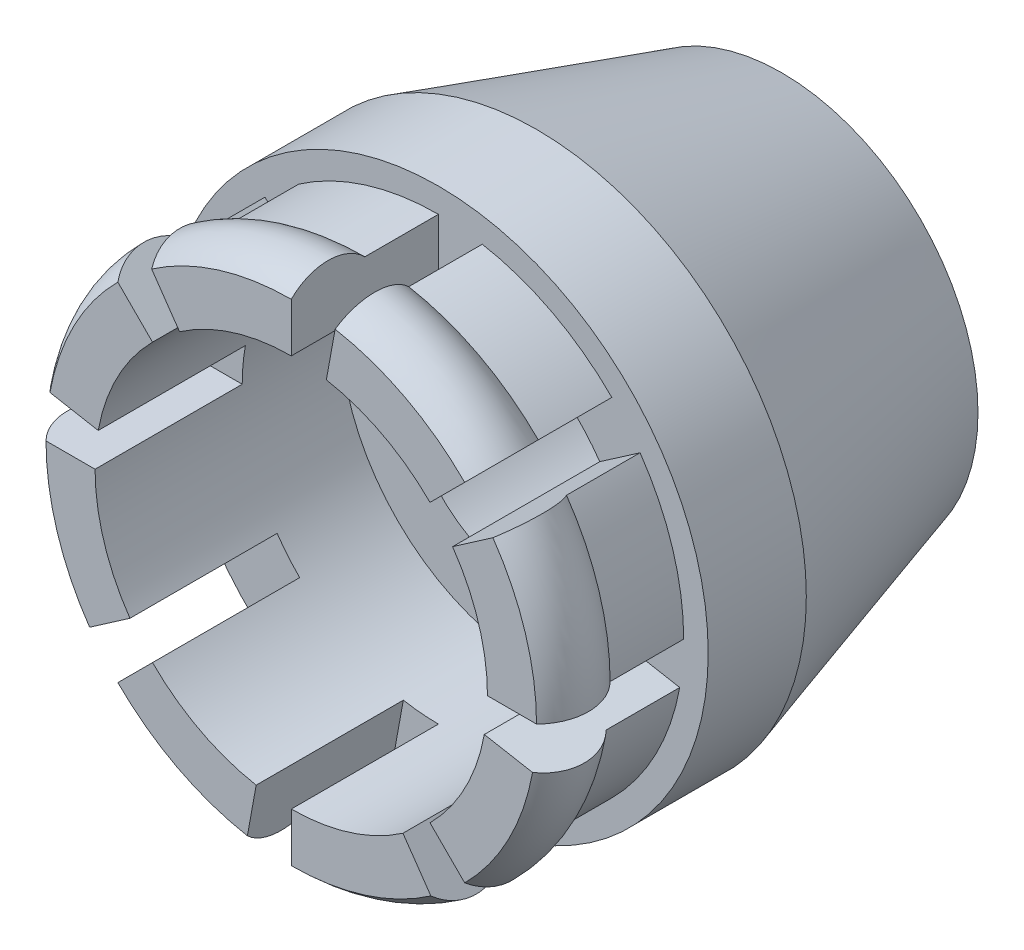
SolidWorks part; units mm, degrees
ref_plane "Front Plane" through (0, 0, 0) normal (0, 0, 1) x (1, 0, 0)
ref_plane "Top Plane" through (0, 0, 0) normal (0, 1, 0) x (1, 0, 0)
ref_plane "Right Plane" through (0, 0, 0) normal (1, 0, 0) x (0, 0, -1)
sketch "Sketch1" plane through (0, 0, 0) normal (0, 0, 1) x (1, 0, 0)
  circle A0 centre (0, 0) radius 2.75
  circle A1 centre (0, 0) radius 5.5
extrude "Boss-Extrude1" add sketch "Sketch1" along normal blind 10
ref_axis "Axis2" through (0, 0, 10) along (0, 0, -1)
sketch "Sketch3" plane through (0, 0, 0) normal (0, 1, 0) x (1, 0, 0)
  line L0 (-5.5, -10) -> (-5, -10)
  line L1 (-5.5, -10) -> (5.5, -10) construction
  line L2 (-5, -8.5) -> (-5, -7)
  line L3 (-5, -7) -> (-5.5, -7)
  line L4 (-5.5, 0) -> (-5.5, -10) construction
  line L5 (-5.5, -7) -> (-5.5, -10)
  line L6 (-5.5, 0) -> (-4, 0)
  line L7 (0, -10) -> (0, 0) construction
  line L8 (-4, -10) -> (0, -10)
  line L9 (-4, -10) -> (-4, -5)
  line L10 (-4, -5) -> (0, -5)
  line L11 (0, -10) -> (0, -5)
  line L12 (5.5, 0) -> (-5.5, 0) construction
  line L13 (-5.5, -5) -> (-4, 0)
  line L14 (-5.5, -5) -> (-5.5, 0)
  arc A0 (-5, -10) -> (-5, -8.5) centre (-4.25, -9.25) cw
revolve "Cut-Revolve1" cut sketch "Sketch3" angle 360 about axis through (0, 0, 10) along (0, 0, -1)
sketch "Sketch4" plane through (0, 0, 10) normal (0, 0, 1) x (1, 0, 0)
  line L0 (0, -4) -> (0, -5.5)
  line L2 (-2.8284, -2.8284) -> (-3.8891, -3.8891)
  line L4 (-4, 0) -> (-5.5, 0)
  line L6 (0, 4) -> (0, 5.5)
  line L8 (2.8284, 2.8284) -> (3.8891, 3.8891)
  line L10 (4, 0) -> (5.5, 0)
  line L17 (-0.9839, -5.4113) -> (-0.7155, -3.9355)
  line L18 (-4.5221, -3.1307) -> (-3.2888, -2.2768)
  line L19 (-5.4113, 0.9839) -> (-3.9355, 0.7155)
  line L21 (0.9839, 5.4113) -> (0.7155, 3.9355)
  line L22 (4.5221, 3.1307) -> (3.2888, 2.2768)
  line L23 (5.4113, -0.9839) -> (3.9355, -0.7155)
  line L24 (2.8284, -2.8284) -> (3.8891, -3.8891)
  line L25 (-2.8284, 2.8284) -> (-3.8891, 3.8891)
  line L28 (3.1307, -4.5221) -> (2.2768, -3.2888)
  line L29 (-3.1307, 4.5221) -> (-2.2768, 3.2888)
  arc A2 (-0.9839, -5.4113) -> (0, -5.5) centre (0, 0) ccw
  arc A3 (3.1307, -4.5221) -> (3.8891, -3.8891) centre (0, 0) ccw
  arc A4 (5.4113, -0.9839) -> (5.5, 0) centre (0, 0) ccw
  arc A5 (4.5221, 3.1307) -> (3.8891, 3.8891) centre (0, 0) ccw
  arc A6 (-4.5221, -3.1307) -> (-3.8891, -3.8891) centre (0, 0) ccw
  arc A7 (-5.4113, 0.9839) -> (-5.5, 0) centre (0, 0) ccw
  arc A8 (0.9839, 5.4113) -> (0, 5.5) centre (0, 0) ccw
  arc A9 (-3.1307, 4.5221) -> (-3.8891, 3.8891) centre (0, 0) ccw
  arc A10 (-0.7155, -3.9355) -> (0, -4) centre (0, 0) ccw
  arc A11 (-3.2888, -2.2768) -> (-2.8284, -2.8284) centre (0, 0) ccw
  arc A12 (-3.9355, 0.7155) -> (-4, 0) centre (0, 0) ccw
  arc A13 (-2.2768, 3.2888) -> (-2.8284, 2.8284) centre (0, 0) ccw
  arc A14 (0.7155, 3.9355) -> (0, 4) centre (0, 0) ccw
  arc A15 (3.2888, 2.2768) -> (2.8284, 2.8284) centre (0, 0) ccw
  arc A16 (3.9355, -0.7155) -> (4, 0) centre (0, 0) ccw
  arc A17 (2.2768, -3.2888) -> (2.8284, -2.8284) centre (0, 0) ccw
extrude "Cut-Extrude1" cut sketch "Sketch4" against normal up to surface (3 mm away) up to face at (5.5, 0, 7)
